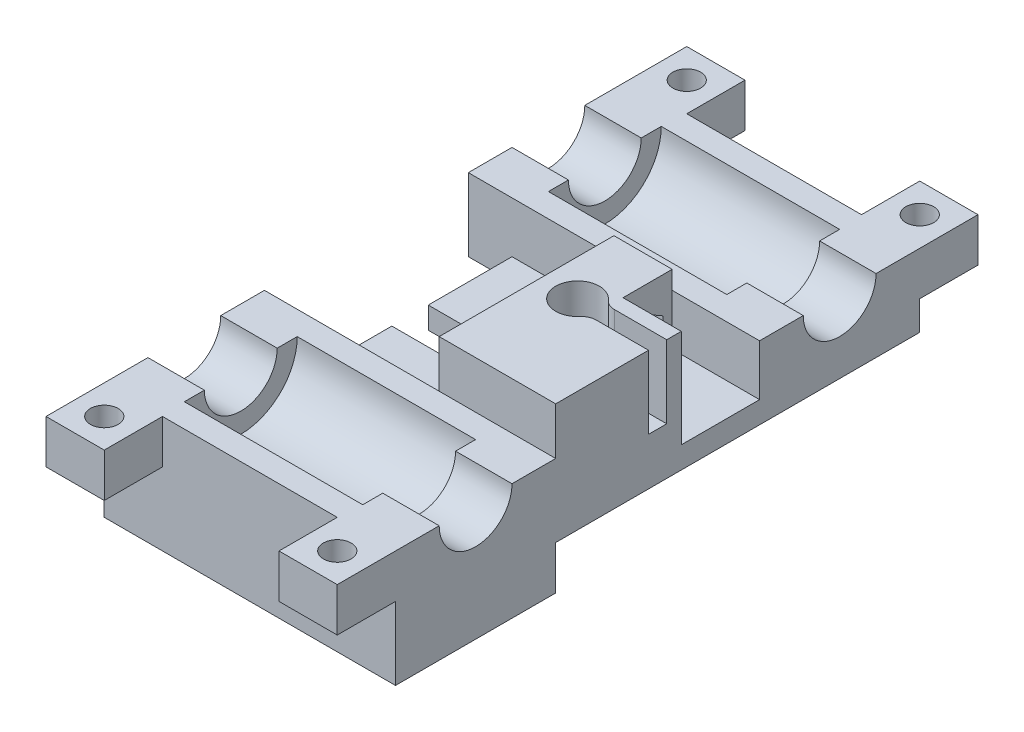
SolidWorks part; units mm, degrees
ref_plane "Front Plane" through (0, 0, 0) normal (0, 0, 1) x (1, 0, 0)
ref_plane "Top Plane" through (0, 0, 0) normal (0, 1, 0) x (1, 0, 0)
ref_plane "Right Plane" through (0, 0, 0) normal (1, 0, 0) x (0, 0, -1)
sketch "Sketch1" plane through (0, 0, 0) normal (0, 1, 0) x (1, 0, 0)
  line L1 (-20, 11) -> (20, 11)
  line L2 (-20, 11) -> (-20, -11)
  line L3 (-20, -11) -> (20, -11)
  line L4 (20, 11) -> (20, -11)
  line L5 (-20, 11) -> (20, -11) construction
  line L6 (-20, -11) -> (20, 11) construction
  point P0 (0, 0)
  dimension "D1" = 40
  dimension "D2" = 22
extrude "Boss-Extrude1" add sketch "Sketch1" along normal blind 11
sketch "Sketch2" plane through (0, 0, 0) normal (0, 1, 0) x (1, 0, 0)
  line L4 (20, -11) -> (20, 11)
  line L5 (-20, -11) -> (20, -11)
  line L6 (-20, 11) -> (-20, -11)
  line L7 (20, 11) -> (-20, 11)
  line L8 (20, -11) -> (20, 11)
  line L9 (-20, -11) -> (20, -11)
  line L10 (-20, 11) -> (-20, -11)
  line L11 (20, 11) -> (-20, 11)
  circle A0 centre (0, 0) radius 4
  dimension "D2" = 8
  dimension "D1" = 0
extrude "Boss-Extrude2" add sketch "Sketch2" against normal blind 5
sketch "Sketch3" plane through (0, 11, 0) normal (0, 1, 0) x (1, 0, 0)
  line L1 (12.25, -7.75) -> (-12.25, -7.75)
  line L2 (12.25, -7.75) -> (12.25, 7.75)
  line L3 (12.25, 7.75) -> (-12.25, 7.75)
  line L4 (-12.25, -7.75) -> (-12.25, 7.75)
  line L5 (12.25, -7.75) -> (-12.25, 7.75) construction
  line L6 (12.25, 7.75) -> (-12.25, -7.75) construction
  point P0 (0, 0)
  dimension "D1" = 15.5
  dimension "D2" = 24.5
extrude "Cut-Extrude1" cut sketch "Sketch3" against normal blind 7.75
fillet "Fillet1" radius 7.75 2 edges at (0, 3.25, 7.75) (0, 3.25, -7.75)
sketch "Sketch4" plane through (-12.25, 0, 0) normal (1, 0, 0) x (0, 0, -1)
  line L0 (7.75, 11) -> (-7.75, 11) construction
  circle A0 centre (0, 11) radius 5
  dimension "D1" = 10
extrude "Cut-Extrude2" cut sketch "Sketch4" against normal through all both and the other way through all
sketch "Sketch5" plane through (0, 11, 0) normal (0, 1, 0) x (1, 0, 0)
  line L1 (20, -11) -> (12, -11)
  line L2 (20, -11) -> (20, -19)
  line L3 (20, -19) -> (12, -19)
  line L4 (12, -11) -> (12, -19)
  circle A0 centre (16, -15) radius 1.9058
  dimension "D1" = 8
  dimension "D2" = 8
  dimension "D3" = 4
  dimension "D4" = 4
extrude "Boss-Extrude3" add sketch "Sketch5" against normal blind 6
sketch "Sketch6" plane through (0, 5, 0) normal (0, -1, 0) x (1, 0, 0)
  line L4 (20, 11) -> (20, 19)
  line L5 (20, 19) -> (12, 19)
  line L6 (12, 19) -> (12, 11)
  line L7 (12, 11) -> (20, 11)
  line L8 (20, 11) -> (20, 19)
  line L9 (20, 19) -> (12, 19)
  line L10 (12, 19) -> (12, 11)
  line L11 (12, 11) -> (20, 11)
  circle A0 centre (16, 15) radius 1.9058 construction
  circle A1 centre (16, 15) radius 1.9058
  circle A2 centre (16, 15) radius 3
  circle M6 centre (16, 15) radius 1.9058
  dimension "D2" = 6
  dimension "D1" = 0
extrude "Cut-Extrude3" cut sketch "Sketch6" against normal blind 3 contours A2 M6 region at (13.0849, 5, 15)
mirror "Mirror8" about plane through (0, 0, 0) normal (1, 0, 0) of "Cut-Extrude3", "Boss-Extrude3"
mirror "Mirror9" [suppressed] about plane through (0, 0, 0) normal (0, 0, 1)
chamfer "Chamfer2" [suppressed] distance 4 angle 45
ref_plane "Plane1" through (0, 0, -25) normal (0, 0, 1) x (1, 0, 0)
sketch "Sketch7" plane through (0, 0, -11) normal (0, 0, -1) x (-1, 0, 0)
  line L0 (-20, 11) -> (-20, -5) construction
  line L1 (-20, 1) -> (-4, 1)
  line L2 (-20, 1) -> (-20, 17.5)
  line L3 (-20, 17.5) -> (-4, 17.5)
  line L4 (-4, 1) -> (-4, 17.5)
  line L5 (-20, 11) -> (20, 11) construction
  dimension "D1" = 16
  dimension "D2" = 16.5
  dimension "D3" = 6.5
extrude "Boss-Extrude5" add sketch "Sketch7" along normal blind 28
mirror "Mirror14" about plane through (0, 0, -25) normal (0, 0, 1) of "Mirror8", "Cut-Extrude3", "Boss-Extrude3", "Cut-Extrude2", "Fillet1", "Cut-Extrude1", "Boss-Extrude2", "Boss-Extrude1"
sketch "Sketch9" plane through (4, 0, 0) normal (-1, 0, 0) x (0, 0, 1)
  line L0 (-39, 1) -> (-39, 11) construction
  line L1 (-11, 1) -> (-39, 1)
  line L2 (-11, 1) -> (-11, 4)
  line L3 (-11, 4) -> (-39, 4)
  line L4 (-39, 1) -> (-39, 4)
  dimension "D1" = 3
extrude "Boss-Extrude6" add sketch "Sketch9" along normal blind 18
sketch "Sketch10" plane through (0, 17.5, 0) normal (0, 1, 0) x (1, 0, 0)
  line L0 (-12.375, 25) -> (12.375, 25) construction
  line L1 (20, 39) -> (20, 11) construction
  line L3 (9, 23.75) -> (20, 23.75)
  line L4 (9, 23.75) -> (9, 26.25)
  line L5 (9, 26.25) -> (20, 26.25)
  line L6 (20, 23.75) -> (20, 26.25)
  circle A0 centre (9, 25) radius 3
  line M4 (20, 11) -> (20, 39)
  dimension "D3" = 6
  dimension "D1" = 0
  dimension "D2" = 11
  dimension "D4" = 2.5
  dimension "D5" = 1.25
extrude "Cut-Extrude4" cut sketch "Sketch10" against normal blind 10 contours L3 A0 L5 L4 | L5 A0 L3 L4 | A0 L3 L5 M4 region at (10.4565, 17.5, -25) region at (8.4952, 17.5, -25) region at (15.955, 17.5, -25)
sketch "Sketch11" plane through (0, 7.5, 0) normal (0, 1, 0) x (1, 0, 0)
  arc A0 (11.7272, 26.25) -> (11.7272, 23.75) centre (9, 25) ccw construction
  arc A1 (11.7272, 26.25) -> (11.7272, 23.75) centre (9, 25) ccw
  circle A2 centre (9, 25) radius 1.75
  dimension "D1" = 3.5
extrude "Cut-Extrude5" cut sketch "Sketch11" against normal through all both and the other way through all contours A2 region at (9, 7.5, -25)
sketch "Sketch12" plane through (4, 0, 0) normal (-1, 0, 0) x (0, 0, 1)
  line L1 (-39, 4) -> (-39, 11) construction
  circle A0 centre (-31, 11) radius 1.75
  dimension "D3" = 3.5
  dimension "D1" = 0
  dimension "D2" = 8
extrude "Cut-Extrude6" cut sketch "Sketch12" against normal through all both and the other way through all
sketch "Sketch15" plane through (20, 0, 0) normal (1, 0, 0) x (0, 0, -1)
  line L1 (32.6923, 13.6869) -> (29.5192, 13.809)
  line L2 (29.5192, 13.809) -> (27.8269, 11.1221)
  line L3 (27.8269, 11.1221) -> (29.3077, 8.3131)
  line L4 (29.3077, 8.3131) -> (32.4808, 8.191)
  line L5 (32.4808, 8.191) -> (34.1731, 10.8779)
  line L6 (34.1731, 10.8779) -> (32.6923, 13.6869)
  circle A0 centre (31, 11) radius 1.75 construction
  circle A1 centre (31, 11) radius 1.75
  circle A2 centre (31, 11) radius 2.75 construction
  dimension "D1" = 5.5
extrude "Cut-Extrude9" [suppressed] cut sketch "Sketch15" against normal blind 12 contours L1 L2 L3 L4 L5 L6
sketch "Sketch16" [suppressed] plane through (20, 0, 0) normal (1, 0, 0) x (0, 0, -1)
  line L1 (27, 11) -> (39, 11)
  line L2 (27, 11) -> (27, 17.5)
  line L3 (27, 17.5) -> (39, 17.5)
  line L4 (39, 11) -> (39, 17.5)
  circle A0 centre (31, 11) radius 1.75 construction
  circle A1 centre (31, 11) radius 1.75
  circle A2 centre (31, 11) radius 4
  dimension "D1" = 8
extrude "Cut-Extrude11" [suppressed] cut sketch "Sketch16" against normal blind 8
chamfer "Chamfer3" [suppressed] distance 2.5 angle 45
fillet "Fillet2" radius 2 2 edges at (11.7272, 12.5, -23.75) (11.7272, 12.5, -26.25)
sketch "Sketch17" plane through (0, 1, 0) normal (0, -1, 0) x (1, 0, 0)
  line L1 (12.1754, -25) -> (10.5877, -22.25)
  line L2 (10.5877, -22.25) -> (7.4123, -22.25)
  line L3 (7.4123, -22.25) -> (5.8246, -25)
  line L4 (5.8246, -25) -> (7.4123, -27.75)
  line L5 (7.4123, -27.75) -> (10.5877, -27.75)
  line L6 (10.5877, -27.75) -> (12.1754, -25)
  circle A0 centre (9, -25) radius 1.75 construction
  circle A1 centre (9, -25) radius 1.75
  circle A2 centre (9, -25) radius 2.75 construction
  dimension "D1" = 5.5
extrude "Cut-Extrude12" cut sketch "Sketch17" against normal blind 3
sketch "Sketch18" plane through (0, 4, 0) normal (0, 1, 0) x (1, 0, 0)
  line L0 (-14, 11) -> (-14, 39) construction
  line L1 (-14, 22.5) -> (4, 22.5)
  line L2 (-14, 22.5) -> (-14, 27.5)
  line L3 (-14, 27.5) -> (4, 27.5)
  line L4 (4, 22.5) -> (4, 27.5)
  line L5 (-12.375, 25) -> (12.375, 25) construction
  dimension "D1" = 2.5
  dimension "D2" = 5
  dimension "D3" = 18
extrude "Cut-Extrude13" cut sketch "Sketch18" against normal through all both and the other way through all
fillet "Fillet3" radius 2.5 2 edges at (4, 2.5, -27.5) (4, 2.5, -22.5)
sketch "Sketch19" plane through (0, 1, 0) normal (0, -1, 0) x (1, 0, 0)
  line L4 (20, -39) -> (-20, -39)
  line L5 (-20, -39) -> (-20, -61)
  line L6 (-20, -61) -> (20, -61)
  line L7 (-14, -22.5) -> (1.5, -22.5)
  line L8 (1.5, -27.5) -> (-14, -27.5)
  line L9 (-14, -27.5) -> (-14, -39)
  line L10 (-14, -39) -> (20, -39)
  line L11 (20, -39) -> (20, -11)
  line L12 (20, -11) -> (-14, -11)
  line L13 (-14, -11) -> (-14, -22.5)
  line L14 (-14, -22.5) -> (1.5, -22.5)
  line L15 (1.5, -27.5) -> (-14, -27.5)
  line L16 (-14, -27.5) -> (-14, -39)
  line L17 (-14, -39) -> (20, -39)
  line L18 (20, -39) -> (20, -11)
  line L19 (20, -11) -> (-14, -11)
  line L20 (-14, -11) -> (-14, -22.5)
  line L21 (20, -61) -> (20, -39)
  line L22 (20, -39) -> (-20, -39)
  line L23 (-20, -39) -> (-20, -61)
  line L24 (-20, -61) -> (20, -61)
  line L25 (20, -61) -> (20, -39)
  arc A2 (4, -25) -> (1.5, -22.5) centre (1.5, -25) ccw
  arc A3 (1.5, -27.5) -> (4, -25) centre (1.5, -25) ccw
  arc A4 (4, -25) -> (1.5, -22.5) centre (1.5, -25) ccw
  arc A5 (1.5, -27.5) -> (4, -25) centre (1.5, -25) ccw
  line M25 (-14, -39) -> (20, -39)
  dimension "D1" = 0
  dimension "D2" = 0
extrude "Cut-Extrude14" cut sketch "Sketch19" along normal through all contours L24 L25 L22 L23 M25 region at (0, 1, -50)
sketch "Sketch20" plane through (0, 17.5, 0) normal (0, 1, 0) x (1, 0, 0)
  line L1 (4, 39) -> (40.1637, 39)
  line L2 (4, 39) -> (4, 35)
  line L3 (4, 35) -> (40.1637, 35)
  line L4 (40.1637, 39) -> (40.1637, 35)
  dimension "D1" = 4
sketch "Sketch21" plane through (20, 0, 0) normal (1, 0, 0) x (0, 0, -1)
  line L1 (31, 14.1754) -> (28.25, 12.5877)
  line L2 (28.25, 12.5877) -> (28.25, 9.4123)
  line L3 (28.25, 9.4123) -> (31, 7.8246)
  line L4 (31, 7.8246) -> (33.75, 9.4123)
  line L5 (33.75, 9.4123) -> (33.75, 12.5877)
  line L6 (33.75, 12.5877) -> (31, 14.1754)
  circle A0 centre (31, 11) radius 1.75 construction
  circle A1 centre (31, 11) radius 1.75
  circle A2 centre (31, 11) radius 2.75 construction
  dimension "D1" = 5.5
extrude "Cut-Extrude15" cut sketch "Sketch21" against normal blind 10
extrude "Cut-Extrude16" cut sketch "Sketch20" against normal up to surface (13.5 mm away) up to face at (-3.5964, 4, -31.7036)
sketch "Sketch22" plane through (20, 0, 0) normal (1, 0, 0) x (0, 0, -1)
  line L0 (28.25, 12.5877) -> (28.25, 9.4123) construction
  line L1 (35, 17.5) -> (28.25, 17.5)
  line L2 (35, 17.5) -> (35, 4)
  line L3 (35, 4) -> (28.25, 4)
  line L4 (28.25, 17.5) -> (28.25, 4)
  line L5 (39, 4) -> (35, 4) construction
  dimension "D1" = 0
  dimension "D2" = 0
extrude "Cut-Extrude18" cut sketch "Sketch22" against normal blind 8
